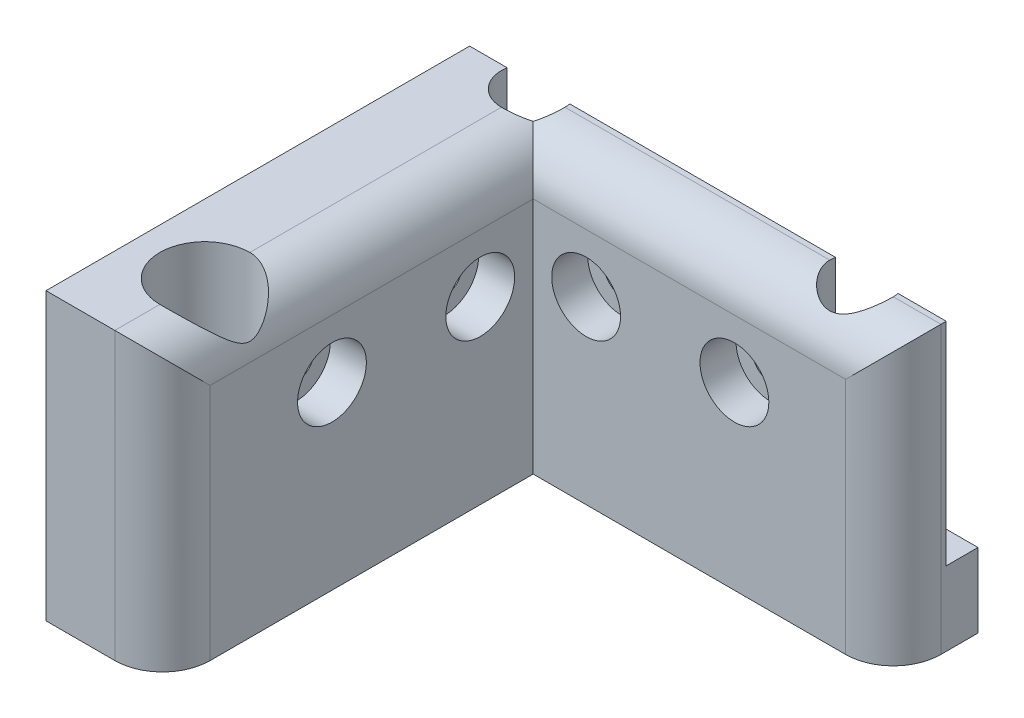
SolidWorks part; units mm, degrees
material "ABS"
ref_plane "Front Plane" through (0, 0, 0) normal (0, 0, 1) x (1, 0, 0)
ref_plane "Top Plane" through (0, 0, 0) normal (0, 1, 0) x (1, 0, 0)
ref_plane "Right Plane" through (0, 0, 0) normal (1, 0, 0) x (0, 0, -1)
sketch "Sketch1" plane through (0, 0, 0) normal (0, 1, 0) x (1, 0, 0)
  line L1 (0, 0) -> (45, 0)
  line L2 (0, 0) -> (0, 40)
  line L3 (0, 40) -> (45, 40)
  line L4 (45, 0) -> (45, 40)
  dimension "D1" = 45
  dimension "D2" = 40
extrude "Boss-Extrude1" add sketch "Sketch1" along normal blind 29
sketch "Sketch33" plane through (0, 29, 0) normal (0, 1, 0) x (1, 0, 0)
  line L0 (0, 40) -> (0, 0) construction
  line L1 (45, 0) -> (11, 0)
  line L2 (45, 0) -> (45, 35)
  line L3 (45, 35) -> (11, 35)
  line L4 (11, 0) -> (11, 35)
  line L5 (45, 40) -> (0, 40) construction
  dimension "D1" = 11
  dimension "D2" = 5
extrude "Cut-Extrude7" cut sketch "Sketch33" against normal through all
sketch "Sketch39" plane through (0, 0, -40) normal (0, 0, -1) x (-1, 0, 0)
  line L0 (0, 29) -> (0, 0) construction
  line L1 (-45, 0) -> (0, 0)
  line L2 (-45, 0) -> (-45, 9)
  line L3 (-45, 9) -> (0, 9)
  line L4 (0, 0) -> (0, 9)
  dimension "D1" = 9
extrude "Boss-Extrude2" add sketch "Sketch39" along normal blind 3
sketch "Sketch21" plane through (0, 29, 0) normal (0, 1, 0) x (1, 0, 0)
  line L0 (45, 40) -> (0, 40) construction
  circle A1 centre (6.5, 39.5) radius 1.75
  circle A2 centre (6.5, 8.5) radius 1.75
  circle A3 centre (37.5, 39.5) radius 1.75
  dimension "D3" = 0.5
  dimension "D4" = 3.5
  dimension "D7" = 3.5
  dimension "D8" = 3.5
  dimension "D1" = 0.5
  dimension "D2" = 31
extrude "Cut-Extrude6" cut sketch "Sketch21" against normal through all both and the other way through all
sketch "Sketch34" plane through (0, 29, 0) normal (0, 1, 0) x (1, 0, 0)
  circle A0 centre (6.5, 8.5) radius 4.25
  circle A1 centre (6.5, 39.5) radius 3
  circle A2 centre (37.5, 39.5) radius 3
  dimension "D1" = 8.5
  dimension "D2" = 6
  dimension "D3" = 6
extrude "Cut-Extrude8" cut sketch "Sketch34" against normal blind 23
hole_wizard "CBORE for M3 Hex Socket Head Cap Screw1" positions "Sketch35" profile "Sketch36" counterbore size "M3" standard "ISO" end condition through all
sketch "Sketch35" plane through (11, 0, 0) normal (1, 0, 0) x (0, 0, -1)
  line L1 (0, 0) -> (0, 29) construction
  line L2 (35, 0) -> (35, 29) construction
  line L3 (35, 29) -> (0, 29) construction
  point P0 (16, 19)
  point P2 (30, 19)
  dimension "D1" = 10
  dimension "D2" = 10
  dimension "D3" = 16
  dimension "D4" = 5
sketch "Sketch36" plane through (11, 19, -16) normal (0, 1, 0) x (0, 0, -1)
  line L0 (0, 0) -> (0, 11)
  line L1 (0, 11) -> (1.7, 11)
  line L3 (1.7, 11) -> (1.7, 3.4)
  line L4 (1.7, 3.4) -> (3.25, 3.4)
  line L5 (3.25, 3.4) -> (3.25, 0)
  line L7 (3.25, 0) -> (0, 0)
  line L11 (0, -6.35) -> (0, 107.95) construction
  dimension "Thru Hole Dia." = 3.4
  dimension "Thru Hole Depth" = 11
  dimension "C'Bore Dia." = 6.5
  dimension "C'Bore Depth" = 3.4
hole_wizard "CBORE for M3 Hex Socket Head Cap Screw2" positions "Sketch37" profile "Sketch38" counterbore size "M3" standard "ISO" end condition through all
sketch "Sketch37" plane through (0, 0, -35) normal (0, 0, 1) x (1, 0, 0)
  line L1 (11, 0) -> (11, 29) construction
  line L2 (45, 0) -> (45, 29) construction
  line L3 (45, 29) -> (11, 29) construction
  point P0 (16, 19)
  point P2 (30, 19)
  dimension "D1" = 10
  dimension "D2" = 10
  dimension "D3" = 5
  dimension "D4" = 15
sketch "Sketch38" plane through (16, 19, -35) normal (1, 0, 0) x (0, -1, 0)
  line L0 (0, 0) -> (0, 8)
  line L1 (0, 8) -> (1.7, 8)
  line L3 (1.7, 8) -> (1.7, 3.4)
  line L4 (1.7, 3.4) -> (3.25, 3.4)
  line L5 (3.25, 3.4) -> (3.25, 0)
  line L7 (3.25, 0) -> (0, 0)
  line L11 (0, -6.35) -> (0, 107.95) construction
  dimension "Thru Hole Dia." = 3.4
  dimension "Thru Hole Depth" = 8
  dimension "C'Bore Dia." = 6.5
  dimension "C'Bore Depth" = 3.4
fillet "Fillet1" radius 4.5 4 edges at (11, 14.5, 0) (45, 14.5, -35) (28, 29, -35) (11, 29, -17.5)
sketch "Sketch40" plane through (0, 0, 0) normal (-1, 0, 0) x (0, 0, 1)
  line L0 (-43, 0) -> (-43, 9) construction
  line L1 (-43, 2) -> (0, 2)
  line L2 (-43, 2) -> (-43, 0)
  line L3 (-43, 0) -> (0, 0)
  line L4 (0, 2) -> (0, 0)
  dimension "D1" = 2
extrude "Cut-Extrude9" cut sketch "Sketch40" against normal through all
sketch "Sketch41" plane through (0, 29, 0) normal (0, 1, 0) x (1, 0, 0)
  line L0 (3.542, 40) -> (0, 40) construction
  line L1 (0, 0) -> (6, 0)
  line L2 (0, 0) -> (0, 40)
  line L3 (0, 40) -> (6, 40)
  line L4 (6, 0) -> (6, 40)
  dimension "D1" = 6
extrude "Cut-Extrude10" [suppressed] cut sketch "Sketch41" against normal blind 20
mirror "Mirror1" [suppressed] of bodies 125 122
delete or keep bodies "Body-Delete/Keep 1" [suppressed] type delete bodies bodies 125
